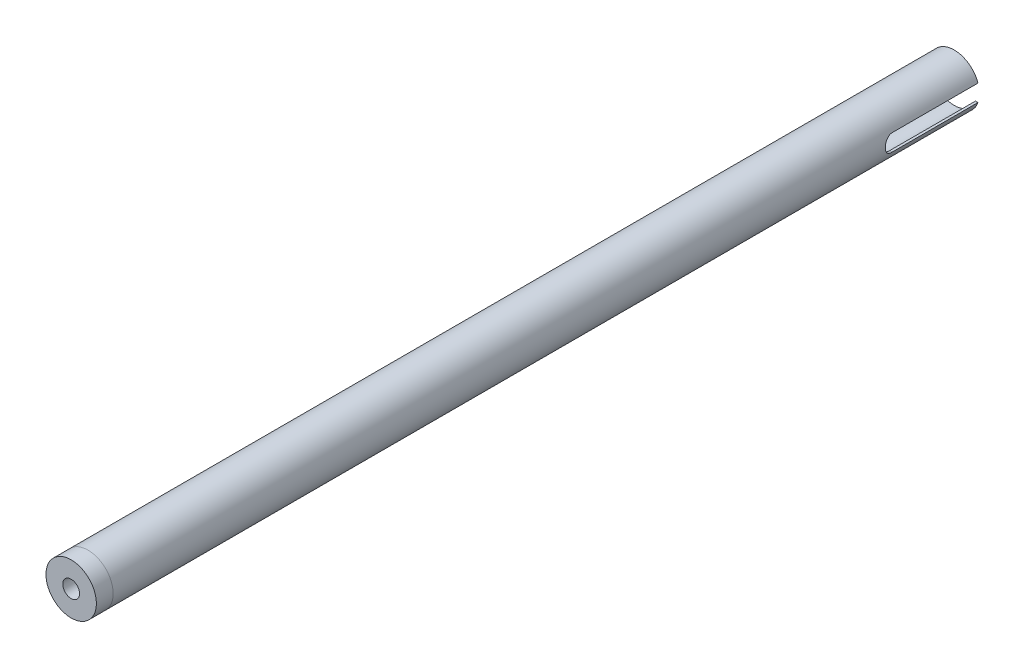
SolidWorks part; units mm, degrees
material "AISI 4130 Steel, normalized at 870C"
ref_plane "Front Plane" through (0, 0, 0) normal (0, 0, 1) x (1, 0, 0)
ref_plane "Top Plane" through (0, 0, 0) normal (0, 1, 0) x (1, 0, 0)
ref_plane "Right Plane" through (0, 0, 0) normal (1, 0, 0) x (0, 0, -1)
sketch "Axis" plane through (0, 0, 0) normal (0, 1, 0) x (1, 0, 0)
  line L0 (0, 0) -> (0, 333.5734) construction
  line L1 (0, 0) -> (0, -21.9075) construction
  line L2 (0, 333.5734) -> (-9.525, 333.5734) construction
  line L4 (0, 368.0751) -> (-10.3187, 330.6983) construction
  dimension "D1" = 21.9075
  dimension "D2" = 9.525
sketch "Sketch1" plane through (0, 0, 0) normal (0, 0, 1) x (1, 0, 0)
  line L0 (-9.525, 0) -> (9.525, 0) construction
  line L1 (-8.9803, 3.175) -> (8.9803, 3.175)
  line L2 (-8.9803, -3.175) -> (8.9803, -3.175)
  circle A0 centre (0, 0) radius 9.525
  circle A1 centre (0, 0) radius 8.636
  circle A2 centre (0, 0) radius 3.175
  dimension "D1" = 19.05
  dimension "D3" = 6.35
  dimension "D2" = 0.889
  dimension "D4" = 6.35
extrude "Threaded insert 1-1" add sketch "Sketch1" against normal blind 6.35 contours A2 L1 A1 | A1 L1 A0 | A2 L0 A1 L1 | A1 L0 A0 L1 | L0 A1 L2 A0 | L0 A2 L2 A1 | A2 L2 A1 | A1 L2 A0 | L0 A1 L2 A2 | L0 A0 L2 A1 | A0 L0 A1 L1 | A1 L0 A2 L1 region at (5.4259, 1.6615, 0) region at (5.4259, -1.6615, 0) region at (8.8881, 1.6046, 0) region at (8.8881, -1.6046, 0) region at (-5.4259, -1.6615, 0) region at (-5.4259, 1.6615, 0) region at (0, 5.4321, 0) region at (0, -5.4321, 0) region at (0, 8.8265, 0) region at (8.5057, -3.3655, 0) region at (-8.8881, -1.6046, 0) region at (-8.8881, 1.6046, 0)
extrude "Threaded insert 1-2" add sketch "Sketch1<3>" against normal blind 6.35 from surface contours A2 L1 A1 | A2 L0 A1 L1 | L0 A2 L2 A1 | A2 L2 A1 | L0 A1 L2 A2 | A1 L0 A2 L1 region at (5.4259, 1.6615, 0) region at (5.4259, -1.6615, 0) region at (-5.4259, -1.6615, 0) region at (-5.4259, 1.6615, 0) region at (0, 5.4321, 0) region at (0, -5.4321, 0) starting at face at (9.525, 0, -6.35)
sketch "Sketch1<3>" plane through (0, 0, 0) normal (0, 0, 1) x (1, 0, 0) same geometry as "Sketch1"
extrude "A-arm tube" add sketch "Sketch1<4>" against normal up to vertex (333.5734 mm away) from surface separate body contours A1 L1 A0 | A1 L0 A0 L1 | L0 A1 L2 A0 | A1 L2 A0 | L0 A0 L2 A1 | A0 L0 A1 L1 region at (8.8881, 1.6046, 0) region at (8.8881, -1.6046, 0) region at (0, 8.8265, 0) region at (8.5057, -3.3655, 0) region at (-8.8881, -1.6046, 0) region at (-8.8881, 1.6046, 0) up to point (0, 0, -333.5734) starting at face at (8.636, 0, -6.35)
sketch "Sketch1<4>" plane through (0, 0, 0) normal (0, 0, 1) x (1, 0, 0) same geometry as "Sketch1"
extrude "Apex slot" cut sketch "Sketch1<5>" along normal blind 35.56 from surface contours A0 L0 A1 L1 | L0 A0 L2 A1 | A1 L0 A0 L1 | L0 A1 L2 A0 region at (8.8881, 1.6046, 0) region at (8.8881, -1.6046, 0) region at (-8.8881, -1.6046, 0) region at (-8.8881, 1.6046, 0) starting at face at (8.636, 0, -333.5734)
sketch "Sketch1<5>" plane through (0, 0, 0) normal (0, 0, 1) x (1, 0, 0) same geometry as "Sketch1"
fillet "Fillet1" radius 3.175 4 edges at (-8.5057, 3.175, -298.0134) (-8.5057, -3.175, -298.0134) (8.5057, -3.175, -298.0134) (8.5057, 3.175, -298.0134)
equation "\"tube diameter\"= 3 / 4"
equation "\"tube thickness\"= .035"
equation "\"apex thickness\"= .25"
equation "\"tube slot\"= 1.4"
equation "\"D1@Sketch1\"=\"tube diameter\""
equation "\"D2@Sketch1\"=\"tube thickness\""
equation "\"threaded insert hole\"= 1 / 4"
equation "\"D3@Sketch1\"=\"threaded insert hole\""
equation "\"D4@Sketch1\"=\"apex thickness\""
equation "\"D1@Apex slot\" = \"tube slot\""
equation "\"D1@Fillet1\"=\"apex thickness\"/2"
equation "\"D2@Axis\"=\"tube diameter\"/2"
